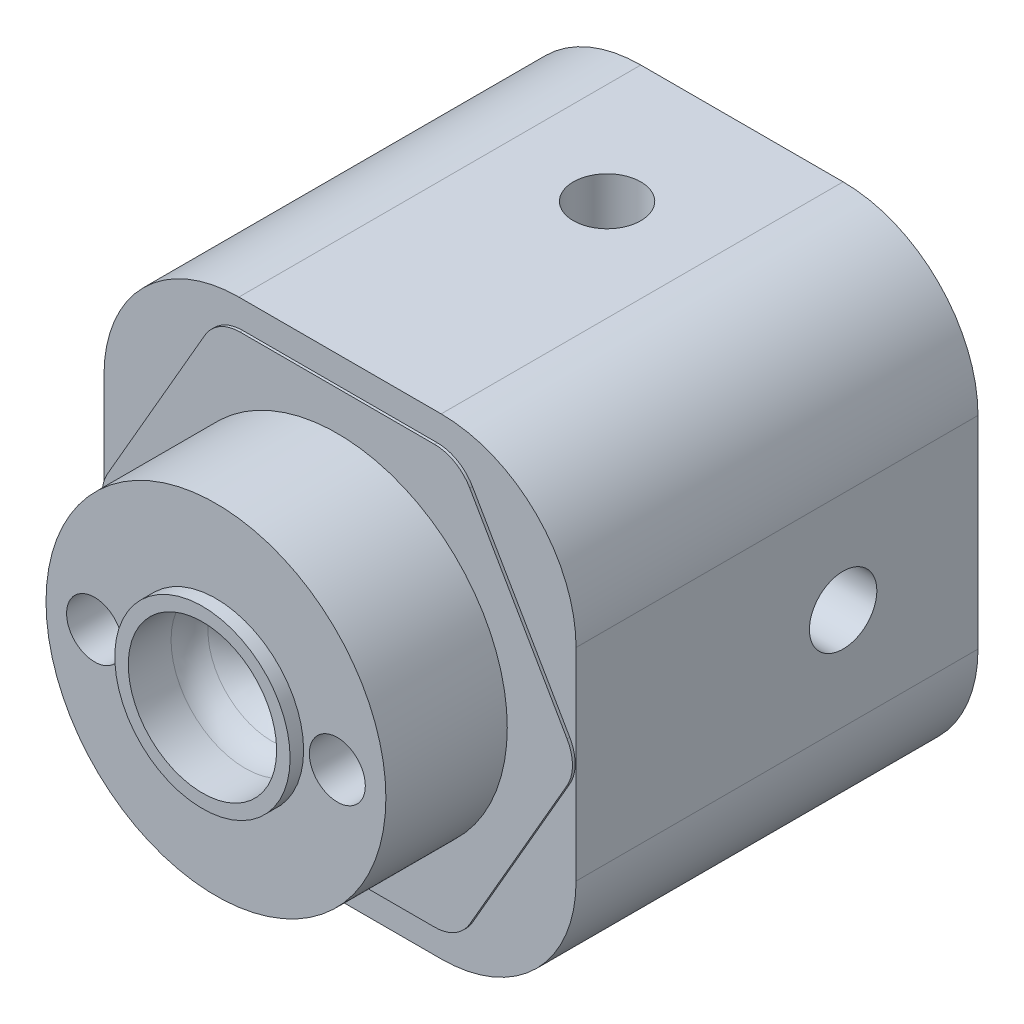
SolidWorks part; units mm, degrees
ref_plane "前视基准面" through (0, 0, 0) normal (0, 0, 1) x (1, 0, 0)
ref_plane "上视基准面" through (0, 0, 0) normal (0, 1, 0) x (1, 0, 0)
ref_plane "右视基准面" through (0, 0, 0) normal (1, 0, 0) x (0, 0, -1)
sketch "草图1" plane through (0, 0, 0) normal (0, 0, 1) x (1, 0, 0)
  circle A0 centre (0, 0) radius 12.6
  dimension "D1" = 25.2
extrude "凸台-拉伸1" add sketch "草图1" along normal blind 9
sketch "草图2" plane through (0, 0, 0) normal (0, 0, -1) x (-1, 0, 0)
  circle A0 centre (0, 0) radius 15
  dimension "D1" = 30
extrude "凸台-拉伸2" add sketch "草图2" along normal blind 5
sketch "草图3" plane through (0, 0, 9) normal (0, 0, 1) x (1, 0, 0)
  circle A0 centre (0, 0) radius 5.5
  dimension "D1" = 11
extrude "切除-拉伸1" cut sketch "草图3" against normal blind 5
sketch "草图4" plane through (0, 0, 9) normal (0, 0, 1) x (1, 0, 0)
  circle A0 centre (-9, 0) radius 2.075
  circle A1 centre (9, 0) radius 2.075
  dimension "D1" = 4.15
  dimension "D2" = 9
  dimension "D3" = 9
extrude "切除-拉伸2" cut sketch "草图4" against normal blind 29
sketch "草图5" plane through (0, 0, 4) normal (0, 0, 1) x (1, 0, 0)
  circle A0 centre (0, 0) radius 3.5
  dimension "D1" = 7
extrude "切除-拉伸3" cut sketch "草图5" against normal blind 31
fillet "圆角1" radius 3 1 edges at (5.5, 0, 4)
fillet "圆角2" radius 5 1 edges at (3.5, 0, 4)
sketch "草图6" plane through (0, 0, 9) normal (0, 0, 1) x (1, 0, 0)
  circle A0 centre (0, 0) radius 5.5
  dimension "D1" = 11
extrude "拉伸-薄壁1" add sketch "草图6" along normal blind 1 thin thin type one direction wall 1
sketch "草图7" plane through (0, 0, -5) normal (0, 0, -1) x (-1, 0, 0)
  line L1 (-8.9489, 15.5) -> (-17.8979, 0)
  line L2 (-17.8979, 0) -> (-8.9489, -15.5)
  line L3 (-8.9489, -15.5) -> (8.9489, -15.5)
  line L4 (8.9489, -15.5) -> (17.8979, 0)
  line L5 (17.8979, 0) -> (8.9489, 15.5)
  line L6 (8.9489, 15.5) -> (-8.9489, 15.5)
  circle A0 centre (0, 0) radius 15.5 construction
  circle A1 centre (0, 0) radius 15
  circle A2 centre (0, 0) radius 15
  dimension "D2" = 31
  dimension "D1" = 0
extrude "凸台-拉伸3" add sketch "草图7" against normal up to surface (5 mm away) up to face at (12.6, 0, 0)
fillet "圆角3" radius 3 6 edges at (17.8979, 0, -2.5) (8.9489, 15.5, -2.5) (-8.9489, 15.5, -2.5) (-17.8979, 0, -2.5) (-8.9489, -15.5, -2.5) (8.9489, -15.5, -2.5)
sketch "草图8" plane through (0, 0, -5) normal (0, 0, -1) x (-1, 0, 0)
  line L6 (-9.815, 14) -> (-17.0318, 1.5)
  line L7 (-17.0318, -1.5) -> (-9.815, -14)
  line L8 (-7.2169, -15.5) -> (7.2169, -15.5)
  line L9 (9.815, -14) -> (17.0318, -1.5)
  line L10 (17.0318, 1.5) -> (9.815, 14)
  line L11 (7.2169, 15.5) -> (-7.2169, 15.5)
  line L12 (-9.815, 14) -> (-17.0318, 1.5)
  line L13 (-17.0318, -1.5) -> (-9.815, -14)
  line L14 (-7.2169, -15.5) -> (7.2169, -15.5)
  line L15 (9.815, -14) -> (17.0318, -1.5)
  line L16 (17.0318, 1.5) -> (9.815, 14)
  line L17 (7.2169, 15.5) -> (-7.2169, 15.5)
  circle A0 centre (0, 0) radius 3.5 construction
  circle A1 centre (0, 0) radius 3.5
  circle A2 centre (-9, 0) radius 4
  circle A3 centre (9, 0) radius 4
  arc A6 (-17.0318, 1.5) -> (-17.0318, -1.5) centre (-14.4338, 0) ccw
  arc A7 (-9.815, -14) -> (-7.2169, -15.5) centre (-7.2169, -12.5) ccw
  arc A8 (7.2169, -15.5) -> (9.815, -14) centre (7.2169, -12.5) ccw
  arc A9 (17.0318, -1.5) -> (17.0318, 1.5) centre (14.4338, 0) ccw
  arc A10 (9.815, 14) -> (7.2169, 15.5) centre (7.2169, 12.5) ccw
  arc A11 (-7.2169, 15.5) -> (-9.815, 14) centre (-7.2169, 12.5) ccw
  arc A12 (-17.0318, 1.5) -> (-17.0318, -1.5) centre (-14.4338, 0) ccw
  arc A13 (-9.815, -14) -> (-7.2169, -15.5) centre (-7.2169, -12.5) ccw
  arc A14 (7.2169, -15.5) -> (9.815, -14) centre (7.2169, -12.5) ccw
  arc A15 (17.0318, -1.5) -> (17.0318, 1.5) centre (14.4338, 0) ccw
  arc A16 (9.815, 14) -> (7.2169, 15.5) centre (7.2169, 12.5) ccw
  arc A17 (-7.2169, 15.5) -> (-9.815, 14) centre (-7.2169, 12.5) ccw
  dimension "D2" = 8
  dimension "D3" = 8
  dimension "D1" = 0
extrude "凸台-拉伸4" add sketch "草图8" along normal blind 5
sketch "草图9" plane through (0, 0, -10) normal (0, 0, -1) x (-1, 0, 0)
  line L1 (-10.05, 10.05) -> (10.05, 10.05)
  line L2 (-10.05, 10.05) -> (-10.05, -10.05)
  line L3 (-10.05, -10.05) -> (10.05, -10.05)
  line L4 (10.05, 10.05) -> (10.05, -10.05)
  line L5 (-10.05, 10.05) -> (10.05, -10.05) construction
  line L6 (-10.05, -10.05) -> (10.05, 10.05) construction
  line L7 (17.5, -17.5) -> (-17.5, -17.5)
  line L8 (17.5, -17.5) -> (17.5, 17.5)
  line L9 (17.5, 17.5) -> (-17.5, 17.5)
  line L10 (-17.5, -17.5) -> (-17.5, 17.5)
  line L11 (17.5, -17.5) -> (-17.5, 17.5) construction
  line L12 (17.5, 17.5) -> (-17.5, -17.5) construction
  point P0 (0, 0)
  point P6 (0, 0)
  dimension "D1" = 20.1
  dimension "D2" = 20.1
  dimension "D3" = 35
  dimension "D4" = 35
extrude "凸台-拉伸5" add sketch "草图9" along normal blind 20
sketch "草图10" plane through (0, 0, -10) normal (0, 0, 1) x (1, 0, 0)
  line L4 (17.5, -17.5) -> (17.5, 17.5)
  line L5 (17.5, 17.5) -> (-17.5, 17.5)
  line L6 (-17.5, 17.5) -> (-17.5, -17.5)
  line L7 (-17.5, -17.5) -> (17.5, -17.5)
  line L8 (17.5, -17.5) -> (17.5, 17.5)
  line L9 (17.5, 17.5) -> (-17.5, 17.5)
  line L10 (-17.5, 17.5) -> (-17.5, -17.5)
  line L11 (-17.5, -17.5) -> (17.5, -17.5)
  line L14 (7.2169, 15.5) -> (-7.2169, 15.5)
  line L15 (17.0318, 1.5) -> (9.815, 14)
  line L16 (9.815, -14) -> (17.0318, -1.5)
  line L17 (-7.2169, -15.5) -> (7.2169, -15.5)
  line L18 (-17.0318, -1.5) -> (-9.815, -14)
  line L19 (-9.815, 14) -> (-17.0318, 1.5)
  line L20 (7.2169, 15.5) -> (-7.2169, 15.5)
  line L21 (17.0318, 1.5) -> (9.815, 14)
  line L22 (9.815, -14) -> (17.0318, -1.5)
  line L23 (-7.2169, -15.5) -> (7.2169, -15.5)
  line L24 (-17.0318, -1.5) -> (-9.815, -14)
  line L25 (-9.815, 14) -> (-17.0318, 1.5)
  arc A6 (9.815, 14) -> (7.2169, 15.5) centre (7.2169, 12.5) ccw
  arc A7 (17.0318, -1.5) -> (17.0318, 1.5) centre (14.4338, 0) ccw
  arc A8 (7.2169, -15.5) -> (9.815, -14) centre (7.2169, -12.5) ccw
  arc A9 (-9.815, -14) -> (-7.2169, -15.5) centre (-7.2169, -12.5) ccw
  arc A10 (-17.0318, 1.5) -> (-17.0318, -1.5) centre (-14.4338, 0) ccw
  arc A11 (-7.2169, 15.5) -> (-9.815, 14) centre (-7.2169, 12.5) ccw
  arc A12 (9.815, 14) -> (7.2169, 15.5) centre (7.2169, 12.5) ccw
  arc A13 (17.0318, -1.5) -> (17.0318, 1.5) centre (14.4338, 0) ccw
  arc A14 (7.2169, -15.5) -> (9.815, -14) centre (7.2169, -12.5) ccw
  arc A15 (-9.815, -14) -> (-7.2169, -15.5) centre (-7.2169, -12.5) ccw
  arc A16 (-17.0318, 1.5) -> (-17.0318, -1.5) centre (-14.4338, 0) ccw
  arc A17 (-7.2169, 15.5) -> (-9.815, 14) centre (-7.2169, 12.5) ccw
  dimension "D1" = 0
  dimension "D2" = 0
extrude "凸台-拉伸6" add sketch "草图10" along normal blind 8.5
fillet "圆角4" radius 10 4 edges at (-17.5, 17.5, -15.75) (-17.5, -17.5, -15.75) (17.5, -17.5, -15.75) (17.5, 17.5, -15.75)
sketch "草图11" plane through (-17.5, 0, 0) normal (-1, 0, 0) x (0, 0, 1)
  line L0 (-30, -7.5) -> (-30, 7.5) construction
  circle A0 centre (-20, 0) radius 2.5
  dimension "D1" = 5
  dimension "D2" = 10
extrude "切除-拉伸4" cut sketch "草图11" against normal blind 15
pattern_circular "阵列(圆周)1" count 4 over 360 about axis through (0, 0, -27) along (0, 0, 1) of "切除-拉伸4"
sketch "草图12" plane through (0, 0, -5) normal (0, 0, -1) x (-1, 0, 0)
  circle A1 centre (9, 0) radius 4
  circle A2 centre (9, 0) radius 4
  circle A3 centre (-9, 0) radius 4
  circle A4 centre (-9, 0) radius 4
  dimension "D1" = 0
  dimension "D2" = 0
extrude "切除-拉伸5" cut sketch "草图12" along normal blind 83
sketch "草图13" plane through (0, 0, -10) normal (0, 0, -1) x (-1, 0, 0)
  line L0 (0, 3.5) -> (0, 10.05)
  line L1 (10.05, 10.05) -> (-10.05, 10.05) construction
  line L2 (0, 0) -> (0, 3.5)
  circle A0 centre (0, 0) radius 3.5 construction
extrude "切除-拉伸-薄壁1" [suppressed] cut sketch "草图13" against normal blind 4 thin thin type mid plane wall 4
fillet "圆角5" [suppressed] radius 4
fillet "圆角6" [suppressed] radius 4
fillet "圆角7" [suppressed] radius 3
sketch "草图14" plane through (0, 0, -1.5) normal (0, 0, 1) x (1, 0, 0)
  line L4 (7.5, 17.5) -> (-7.5, 17.5)
  line L5 (-17.5, 7.5) -> (-17.5, -7.5)
  line L6 (-7.5, -17.5) -> (7.5, -17.5)
  line L7 (17.5, -7.5) -> (17.5, 7.5)
  line L8 (7.5, 17.5) -> (-7.5, 17.5)
  line L9 (-17.5, 7.5) -> (-17.5, -7.5)
  line L10 (-7.5, -17.5) -> (7.5, -17.5)
  line L11 (17.5, -7.5) -> (17.5, 7.5)
  line L14 (9.815, -14) -> (17.0318, -1.5)
  line L15 (17.0318, 1.5) -> (9.815, 14)
  line L16 (7.2169, 15.5) -> (-7.2169, 15.5)
  line L17 (-9.815, 14) -> (-17.0318, 1.5)
  line L18 (-17.0318, -1.5) -> (-9.815, -14)
  line L19 (-7.2169, -15.5) -> (7.2169, -15.5)
  line L20 (9.815, -14) -> (17.0318, -1.5)
  line L21 (17.0318, 1.5) -> (9.815, 14)
  line L22 (7.2169, 15.5) -> (-7.2169, 15.5)
  line L23 (-9.815, 14) -> (-17.0318, 1.5)
  line L24 (-17.0318, -1.5) -> (-9.815, -14)
  line L25 (-7.2169, -15.5) -> (7.2169, -15.5)
  arc A4 (-7.5, 17.5) -> (-17.5, 7.5) centre (-7.5, 7.5) ccw
  arc A5 (-17.5, -7.5) -> (-7.5, -17.5) centre (-7.5, -7.5) ccw
  arc A6 (7.5, -17.5) -> (17.5, -7.5) centre (7.5, -7.5) ccw
  arc A7 (17.5, 7.5) -> (7.5, 17.5) centre (7.5, 7.5) ccw
  arc A8 (-7.5, 17.5) -> (-17.5, 7.5) centre (-7.5, 7.5) ccw
  arc A9 (-17.5, -7.5) -> (-7.5, -17.5) centre (-7.5, -7.5) ccw
  arc A10 (7.5, -17.5) -> (17.5, -7.5) centre (7.5, -7.5) ccw
  arc A11 (17.5, 7.5) -> (7.5, 17.5) centre (7.5, 7.5) ccw
  arc A14 (17.0318, -1.5) -> (17.0318, 1.5) centre (14.4338, 0) ccw
  arc A15 (9.815, 14) -> (7.2169, 15.5) centre (7.2169, 12.5) ccw
  arc A16 (-7.2169, 15.5) -> (-9.815, 14) centre (-7.2169, 12.5) ccw
  arc A17 (-17.0318, 1.5) -> (-17.0318, -1.5) centre (-14.4338, 0) ccw
  arc A18 (-9.815, -14) -> (-7.2169, -15.5) centre (-7.2169, -12.5) ccw
  arc A19 (7.2169, -15.5) -> (9.815, -14) centre (7.2169, -12.5) ccw
  arc A20 (17.0318, -1.5) -> (17.0318, 1.5) centre (14.4338, 0) ccw
  arc A21 (9.815, 14) -> (7.2169, 15.5) centre (7.2169, 12.5) ccw
  arc A22 (-7.2169, 15.5) -> (-9.815, 14) centre (-7.2169, 12.5) ccw
  arc A23 (-17.0318, 1.5) -> (-17.0318, -1.5) centre (-14.4338, 0) ccw
  arc A24 (-9.815, -14) -> (-7.2169, -15.5) centre (-7.2169, -12.5) ccw
  arc A25 (7.2169, -15.5) -> (9.815, -14) centre (7.2169, -12.5) ccw
  dimension "D1" = 0
  dimension "D2" = 0
extrude "凸台-拉伸7" add sketch "草图14" along normal blind 1.3
sketch "草图15" plane through (0, 0, -10) normal (0, 0, -1) x (-1, 0, 0)
  line L1 (-22.4047, 19.5466) -> (22.4047, 19.5466)
  line L2 (-22.4047, 19.5466) -> (-22.4047, -19.5466)
  line L3 (-22.4047, -19.5466) -> (22.4047, -19.5466)
  line L4 (22.4047, 19.5466) -> (22.4047, -19.5466)
  line L5 (-22.4047, 19.5466) -> (22.4047, -19.5466) construction
  line L6 (-22.4047, -19.5466) -> (22.4047, 19.5466) construction
  point P0 (0, 0)
extrude "切除-拉伸6" [suppressed] cut sketch "草图15" along normal blind 34
sketch "草图16" plane through (0, 0, -10) normal (0, 0, -1) x (-1, 0, 0)
  line L1 (15, -12) -> (-15, -12)
  line L2 (15, -12) -> (15, 12)
  line L3 (15, 12) -> (-15, 12)
  line L4 (-15, -12) -> (-15, 12)
  line L5 (15, -12) -> (-15, 12) construction
  line L6 (15, 12) -> (-15, -12) construction
  point P0 (0, 0)
  dimension "D1" = 24
  dimension "D2" = 30
extrude "凸台-拉伸8" [suppressed] add sketch "草图16" along normal blind 34
